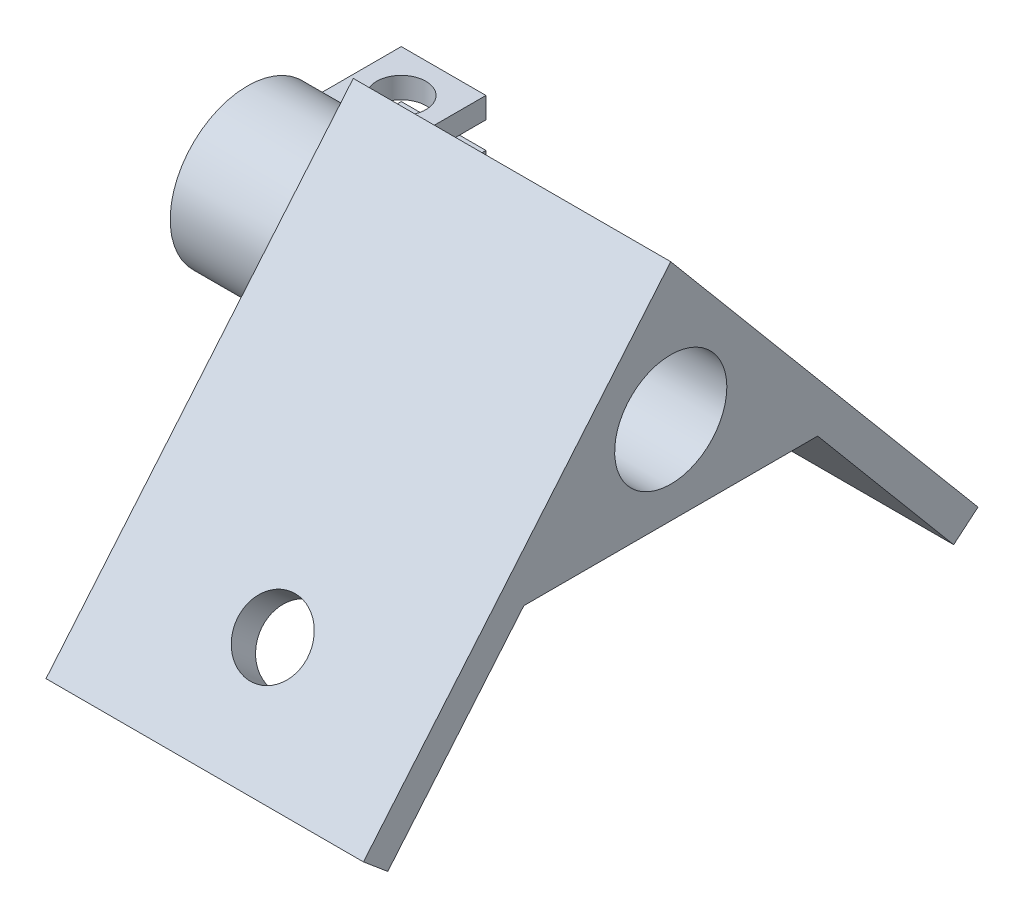
SolidWorks part; units mm, degrees
material "PLA Black"
ref_plane "Front" through (0, 0, 0) normal (0, 0, 1) x (1, 0, 0)
ref_plane "Top" through (0, 0, 0) normal (0, 1, 0) x (1, 0, 0)
ref_plane "Right" through (0, 0, 0) normal (1, 0, 0) x (0, 0, -1)
sketch "Sketch1" plane through (0, 0, 0) normal (1, 0, 0) x (0, 0, -1)
  line L0 (0, 12.9125) -> (-29.0371, -21.6925)
  line L1 (-29.0371, -21.6925) -> (-26.7389, -23.6209)
  line L2 (-26.7389, -23.6209) -> (-13.8832, -8.3)
  line L3 (-13.8832, -8.3) -> (13.8832, -8.3)
  line L4 (0, 31.2499) -> (0, -31.1028) construction
  line L5 (26.7389, -23.6209) -> (13.8832, -8.3)
  line L6 (0, 12.9125) -> (29.0371, -21.6925)
  line L7 (29.0371, -21.6925) -> (26.7389, -23.6209)
  circle A0 centre (0, 0) radius 5.3
  dimension "D1" = 10.6
  dimension "D4" = 3
  dimension "D2" = 40
  dimension "D3" = 3
  dimension "D5" = 3
  dimension "D6" = 20
extrude "Boss-Extrude1" add sketch "Sketch1" along normal mid plane 30
hole_wizard "M6 Clearance Hole1" positions "Sketch3" profile "Sketch4" hole size "M6" standard "DIN" end condition through all
sketch "Sketch3" plane through (0, 3.4068, 4.06) normal (0, -0.6428, -0.766) x (-1, 0, 0)
  line L0 (-34.564, -25.2821) -> (6.8322, -25.2821) construction
  line L2 (0, -15.2821) -> (0, -35.2821) construction
  line L3 (-15, -15.2821) -> (15, -15.2821) construction
  line L4 (-15, -35.2821) -> (15, -35.2821) construction
  point P0 (0, -25.2821)
sketch "Sketch4" plane through (0, -15.9604, 20.3111) normal (1, 0, 0) x (0, 0.766, -0.6428)
  line L0 (0, 0) -> (0, 25.2437)
  line L1 (0, 25.2437) -> (3.3, 25.2437)
  line L2 (3.3, 25.2437) -> (3.3, 0)
  line L5 (3.3, 0) -> (0, 0)
  line L11 (0, -6.35) -> (0, 107.95) construction
  dimension "Thru Hole Dia." = 6.6
  dimension "Thru Hole Depth" = 25.2437
mirror "Mirror1" about plane through (0, 0, 0) normal (0, 0, 1) of "M6 Clearance Hole1"
sketch "Sketch7" plane through (-15, 0, 0) normal (-1, 0, 0) x (0, 0, 1)
  line L0 (-5.1505, 1.25) -> (-7.1922, 1.25)
  line L1 (-5.1505, -1.25) -> (-7.1922, -1.25)
  line L2 (0, 0) -> (-15.3745, 0) construction
  arc A0 (-5.1505, -1.25) -> (-5.1505, 1.25) centre (0, 0) ccw
  arc A1 (-7.1922, -1.25) -> (-7.1922, 1.25) centre (0, 0) ccw
  circle A2 centre (0, 0) radius 5.3 construction
  dimension "D1" = 2
  dimension "D2" = 2.5
extrude "Boss-Extrude3" add sketch "Sketch7" along normal blind 2
sketch "Sketch5" plane through (-17, 0, 0) normal (-1, 0, 0) x (0, 0, 1)
  line L0 (-5.1505, 1.25) -> (-14.5366, 1.25)
  line L1 (-14.5366, 1.25) -> (-14.5366, 3.25)
  line L2 (-14.5366, 3.25) -> (-6.5366, 3.25)
  line L3 (0, 0) -> (-16.2155, 0) construction
  line L4 (-6.5366, -3.25) -> (-6.5366, -10.25)
  line L5 (-14.5366, -1.25) -> (-14.5366, -10.25)
  line L6 (-5.1505, -1.25) -> (-14.5366, -1.25)
  line L7 (-6.5366, -10.25) -> (-14.5366, -10.25)
  circle A0 centre (0, 0) radius 5.3 construction
  arc A1 (-6.5366, 3.25) -> (-6.5366, -3.25) centre (0, 0) cw
  arc A2 (-5.1505, 1.25) -> (-5.1505, -1.25) centre (0, 0) cw
  dimension "D1" = 2
  dimension "D2" = 8
  dimension "D3" = 2.5
  dimension "D4" = 2
  dimension "D5" = 9
extrude "Boss-Extrude2" add sketch "Sketch5" along normal blind 8
sketch "Sketch6" plane through (0, 3.25, 0) normal (0, 1, 0) x (1, 0, 0)
  line L0 (-21, 14.5366) -> (-21, 6.5366) construction
  line L1 (-25, 14.5366) -> (-17, 14.5366) construction
  line L2 (-25, 6.5366) -> (-17, 6.5366) construction
  circle A0 centre (-21, 10.5366) radius 2.325
  dimension "D1" = 4.65
extrude "Cut-Extrude1" cut sketch "Sketch6" against normal through all
